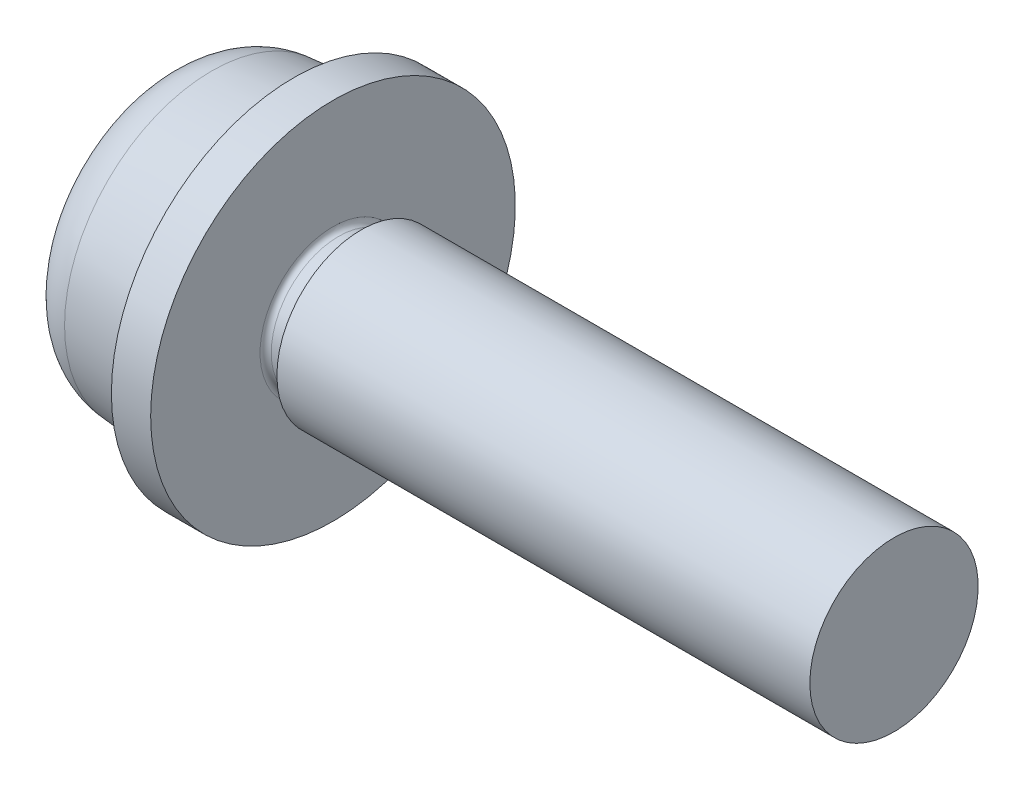
SolidWorks part; units mm, degrees
other "詳細ｱｲﾃﾑ1"
ref_plane "z0" through (0, 0, 0) normal (0, 0, 1) x (1, 0, 0)
ref_plane "y0" through (0, 0, 0) normal (0, 1, 0) x (1, 0, 0)
ref_plane "x0" through (0, 0, 0) normal (1, 0, 0) x (0, 0, -1)
sketch "ｽｹｯﾁ1" plane through (0, 0, 0) normal (0, 0, 1) x (1, 0, 0)
  line L0 (0, 0) -> (30.0467, 0) construction
  line L1 (-2.1627, 2.622) -> (-0.7, 2.75)
  line L2 (0, 3.25) -> (0, 1.2)
  line L3 (10, 0) -> (-3.3, 0)
  line L4 (0, 1.2) -> (0.5, 1.2)
  line L5 (0.5, 1.2) -> (0.5, 1.5)
  line L6 (0.5, 1.5) -> (10, 1.5)
  line L7 (10, 1.5) -> (10, 0)
  line L8 (0, 3.25) -> (-0.7, 3.25)
  line L10 (-0.7, 3.25) -> (-0.7, 2.75)
  arc A0 (-3.0381, 1.8968) -> (-3.3, 0) centre (3.7, 0) ccw
  arc A1 (-3.0381, 1.8968) -> (-2.1627, 2.622) centre (-2.0755, 1.6258) cw
  point P16 (-2.8131, 2.5651)
  dimension "D11" = 7
  dimension "D5" = 0.5
  dimension "D7" = 10
  dimension "D3" = 3.3
  dimension "D1" = 0.4869
  dimension "D4" = 3
  dimension "D8" = 85
  dimension "D6" = 2.4
  dimension "D2" = 6.5
  dimension "D10" = 0.7
  dimension "D9" = 5.5
revolve "ﾍﾞｰｽ -回転" add sketch "ｽｹｯﾁ1" angle 360 about L0
cosmetic thread "ねじ山1" parameters "D2"=2.4
ref_plane "平面4" through (-3.3, 0, 0) normal (1, 0, 0) x (0, 0, -1)
sketch "ｽｹｯﾁ2" plane through (-3.3, 0, 0) normal (1, 0, 0) x (0, 0, -1)
  line L0 (0.515, -1.85) -> (-0.515, -1.85)
  line L1 (0.515, -1.85) -> (0.515, -0.815)
  line L2 (-0.515, 1.85) -> (0.515, 1.85)
  line L3 (-0.515, 1.85) -> (-0.515, 0.815)
  line L4 (1.85, -0.515) -> (0.815, -0.515)
  line L5 (1.85, -0.515) -> (1.85, 0.515)
  line L6 (-1.85, 0.515) -> (-0.815, 0.515)
  line L7 (-1.85, 0.515) -> (-1.85, -0.515)
  line L8 (1.85, 0) -> (-1.85, 0) construction
  line L9 (0, 1.85) -> (0, -1.85) construction
  line L10 (0.815, 0.515) -> (1.85, 0.515)
  line L11 (-0.815, -0.515) -> (-1.85, -0.515)
  line L12 (0.515, 0.815) -> (0.515, 1.85)
  line L13 (-0.515, -0.815) -> (-0.515, -1.85)
  arc A0 (-0.815, 0.515) -> (-0.515, 0.815) centre (-0.815, 0.815) ccw
  arc A1 (0.815, 0.515) -> (0.515, 0.815) centre (0.815, 0.815) cw
  arc A2 (0.515, -0.815) -> (0.815, -0.515) centre (0.815, -0.815) cw
  arc A3 (-0.815, -0.515) -> (-0.515, -0.815) centre (-0.815, -0.815) cw
  point P21 (0.515, 0.515)
  point P26 (-0.515, -0.515)
  dimension "D3" = 0.3
  dimension "D1" = 1.03
  dimension "D2" = 3.7
extrude "ｶｯﾄ - 押し出し1" cut sketch "ｽｹｯﾁ2" along normal blind 1.53 draft 10
fillet "ﾌｨﾚｯﾄ1" radius 0.1 1 edges at (0, 0, 1.2)
sketch "ｽｹｯﾁ3" plane through (10, 0, 0) normal (1, 0, 0) x (0, 0, -1)
  circle A0 centre (0, 0) radius 1.5 construction
  circle A1 centre (0, 0) radius 1.5
  circle A2 centre (0, 0) radius 1.2
  dimension "D1" = 2.4
extrude "ｶｯﾄ - 押し出し2" [suppressed] cut sketch "ｽｹｯﾁ3" against normal blind 10
sketch "ｽｹｯﾁ4" plane through (0, 0, 0) normal (1, 0, 0) x (0, 0, -1)
  line L1 (0, 3.4641) -> (-3, 1.7321)
  line L2 (-3, 1.7321) -> (-3, -1.7321)
  line L3 (-3, -1.7321) -> (0, -3.4641)
  line L4 (0, -3.4641) -> (3, -1.7321)
  line L5 (3, -1.7321) -> (3, 1.7321)
  line L6 (3, 1.7321) -> (0, 3.4641)
  circle A0 centre (0, 0) radius 3 construction
  dimension "D1" = 6
extrude "ｶｯﾄ - 押し出し3" [suppressed] cut sketch "ｽｹｯﾁ4" against normal through all from offset 1 flip side to cut offset against normal yes
equation "\"D1@ｶｯﾄ - 押し出し2\" = \"D7@ｽｹｯﾁ1\""
equation "\"D1@平面4\" = \"D3@ｽｹｯﾁ1\""
